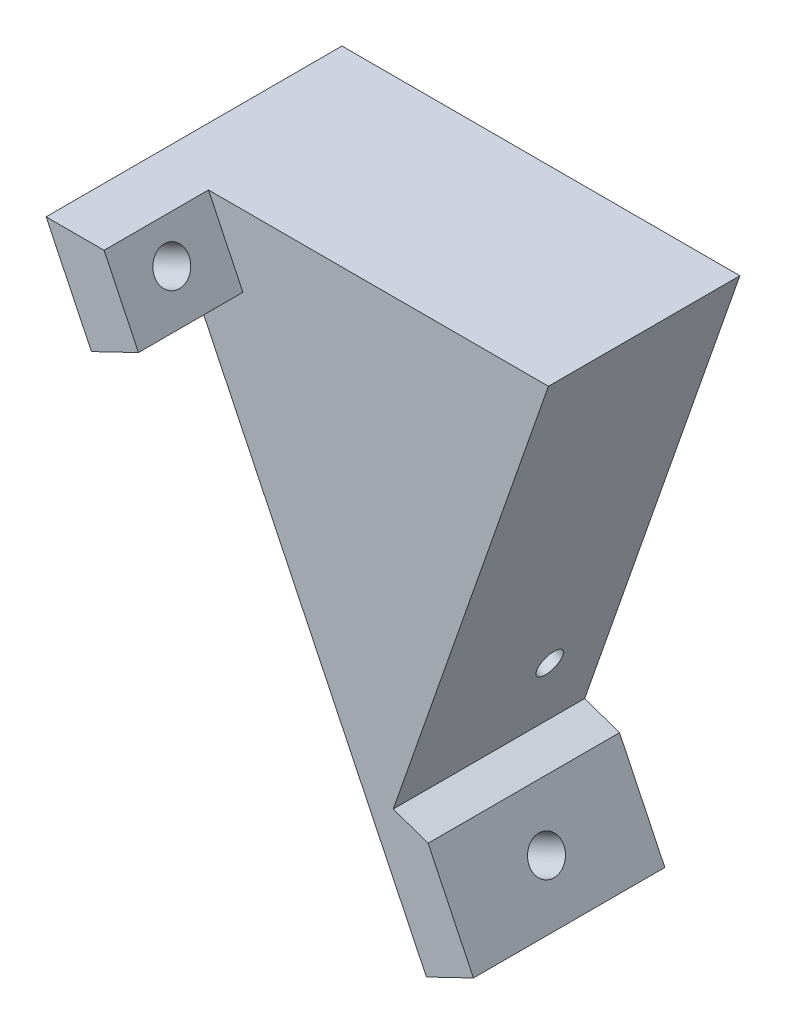
SolidWorks part; units mm, degrees
material "ABS"
ref_plane "Front Plane" through (0, 0, 0) normal (0, 0, 1) x (1, 0, 0)
ref_plane "Top Plane" through (0, 0, 0) normal (0, 1, 0) x (1, 0, 0)
ref_plane "Right Plane" through (0, 0, 0) normal (1, 0, 0) x (0, 0, -1)
sketch "Sketch1" plane through (0, 0, 0) normal (0, 0, 1) x (1, 0, 0)
  line L0 (-36.2386, 24.2413) -> (-9.7428, -30.7587)
  line L1 (-9.7428, -30.7587) -> (9.4941, 24.2413)
  line L2 (9.4941, 24.2413) -> (-36.2386, 24.2413)
  dimension "D1" = 55
  dimension "D2" = 55
  dimension "D3" = 45
extrude "Boss-Extrude1" add sketch "Sketch1" along normal blind 22
sketch "Sketch6" plane through (-19.9343, -9.6032, 0) normal (-0.9009, -0.434, 0) x (0, 0, 1)
  line L0 (22, 37.5671) -> (22, -23.4823) construction
  line L1 (34, 37.5671) -> (22, 37.5671)
  line L2 (34, 37.5671) -> (34, 25.5671)
  line L3 (34, 25.5671) -> (22, 25.5671)
  line L4 (22, 37.5671) -> (22, 25.5671)
  line L5 (0, -23.4823) -> (22, -23.4823)
  line L6 (0, -23.4823) -> (0, -35.4823)
  line L7 (0, -35.4823) -> (22, -35.4823)
  line L8 (22, -23.4823) -> (22, -35.4823)
  line L9 (22, 37.5671) -> (0, 37.5671) construction
  dimension "D1" = 12
  dimension "D2" = 12
  dimension "D3" = 0
  dimension "D4" = 12
  dimension "D5" = 0
  dimension "D6" = 0
extrude "Boss-Extrude4" add sketch "Sketch6" against normal blind 6
sketch "Sketch8" plane through (0, 0, 0) normal (0, 0, -1) x (-1, 0, 0)
  line L0 (9.7428, -30.7587) -> (4.3373, -28.1546)
  line L1 (4.3373, -28.1546) -> (8.3431, -26.7568)
  line L2 (9.7428, -30.7587) -> (-9.4941, 24.2413) construction
  line L3 (8.3431, -26.7568) -> (9.7428, -30.7587)
extrude "Boss-Extrude5" add sketch "Sketch8" against normal up to vertex (22 mm away) up to point (-9.7428, -30.7587, 22)
sketch "Sketch9" plane through (-14.5288, -6.9992, 0) normal (0.9009, 0.434, 0) x (0, 0, -1)
  line L2 (-22, 25.5671) -> (-34, 25.5671) construction
  line L3 (0, -35.4823) -> (-22, -35.4823) construction
  line L4 (-22, -35.4823) -> (-22, -23.4823) construction
  circle A0 centre (-28, 30.5671) radius 2
  circle A1 centre (-11, -29.4823) radius 2
  point P9 (-28, 25.5671)
  point P12 (-11, -35.4823)
  point P15 (-22, -29.4823)
  dimension "D1" = 4
  dimension "D2" = 4
  dimension "D3" = 5
  dimension "D4" = 0
  dimension "D5" = 0
  dimension "D6" = 0
extrude "Cut-Extrude9" cut sketch "Sketch9" against normal blind 6
sketch "Sketch10" plane through (0.9048, -0.3164, 0) normal (0.9439, -0.3301, 0) x (0, 0, -1)
  line L0 (-22, 26.0166) -> (0, 26.0166) construction
  line L1 (0, -28.011) -> (0, 26.0166) construction
  circle A0 centre (-7, -18.9834) radius 1.5
  dimension "D1" = 3
  dimension "D3" = 7
  dimension "D2" = 45
extrude "Cut-Extrude10" cut sketch "Sketch10" against normal blind 36
sketch "Sketch12" plane through (0, 0, 22) normal (0, 0, -1) x (-1, 0, 0)
  line L0 (30.8332, 26.8454) -> (29.5787, 24.2413)
  line L1 (29.5787, 24.2413) -> (36.2386, 24.2413)
  line L2 (36.2386, 24.2413) -> (30.8332, 26.8454)
extrude "Cut-Extrude11" cut sketch "Sketch12" against normal blind 20
